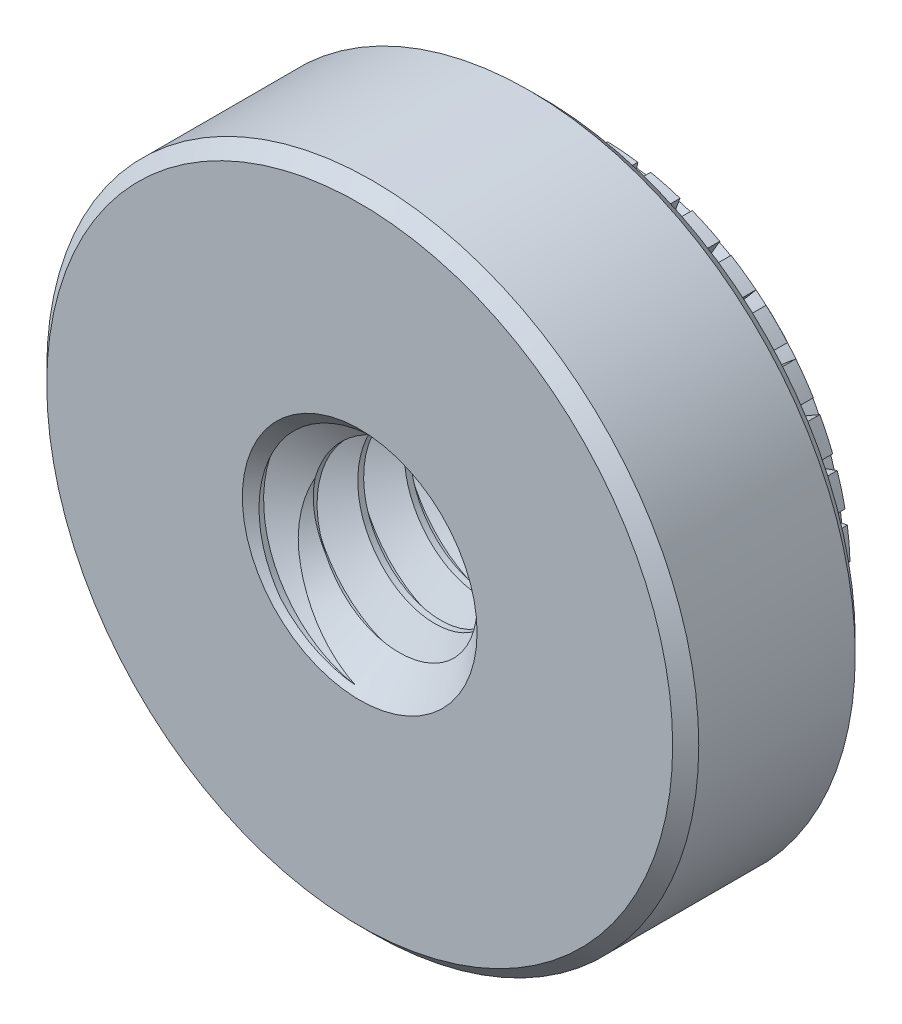
SolidWorks part; units mm, degrees
ref_plane "Front Plane" through (0, 0, 0) normal (0, 0, 1) x (1, 0, 0)
ref_plane "Top Plane" through (0, 0, 0) normal (0, 1, 0) x (1, 0, 0)
ref_plane "Right Plane" through (0, 0, 0) normal (1, 0, 0) x (0, 0, -1)
sketch "Sketch1" plane through (0, 0, 0) normal (0, 0, 1) x (1, 0, 0)
  circle A0 centre (0, 0) radius 3.175
  dimension "A" = 6.35
extrude "Extrude1" add sketch "Sketch1" against normal blind 1.778
sketch "Sketch15" plane through (0, 0, -1.778) normal (0, 0, -1) x (-1, 0, 0)
  circle A0 centre (0, 0) radius 2.1082
  dimension "hole dia" = 4.2164
sketch "Sketch2" plane through (0, 0, -1.778) normal (0, 0, -1) x (-1, 0, 0)
  circle A0 centre (0, 0) radius 2.4257
  dimension "D1" = 4.8514
extrude "Extrude2" add sketch "Sketch2" along normal blind 0.762
sketch "Sketch3" plane through (0, 0, -2.54) normal (0, 0, -1) x (-1, 0, 0)
  line L0 (0, 2.2352) -> (0, 3.175)
  circle A1 centre (0, 0) radius 3.175 construction
  circle A2 centre (0, 0) radius 2.2352
  circle A3 centre (0, 0) radius 2.2352 construction
  dimension "D1" = 0.1905
extrude "Cut-Extrude-Thin1" cut sketch "Sketch3" against normal up to surface (0.762 mm away) thin up to face at (3.175, 0, -1.778) thin type mid plane wall 0.127
pattern_circular "CirPattern1" count 36 over 360 about axis through (0, 0, -1.778) along (0, 0, 1) of "Cut-Extrude-Thin1"
sketch "Sketch5" plane through (0, 0, -2.54) normal (0, 0, -1) x (-1, 0, 0)
  circle A0 centre (0, 0) radius 3.175 construction
  circle A3 centre (0, 0) radius 2.159
  dimension "C" = 4.318
extrude "Cut-Extrude1" cut sketch "Sketch5" against normal blind 0.1905 draft 20 flip side to cut draft outward yes
chamfer "Chamfer2" distance 0.127 angle 45 2 edges at (3.175, 0, 0) (3.175, 0, -1.778)
sketch "Sketch7" plane through (0, 0, 0) normal (0, 0, 1) x (1, 0, 0)
  circle A0 centre (0, 0) radius 1.0922
  dimension "Thread Od" = 2.1844
extrude "Cut-Extrude3" cut sketch "Sketch7" against normal through all
sketch "Sketch8" plane through (0, 0, -2.54) normal (0, 0, -1) x (-1, 0, 0)
  circle A0 centre (0, 0) radius 1.0922 construction
  circle A1 centre (0, 0) radius 1.0922
curve "Helix/Spiral1" pitch 0.4536 height 5.715 radius 1.0922 centre (0, 0, -2.54) axis (0, 0, 1) start towards (0, 1, 0) parameters "pitch"=0.4536
sketch "Sketch9" plane through (0, 0, 0) normal (1, 0, 0) x (0, 0, -1)
  line L0 (2.9369, 1.0922) -> (2.7668, 0.7976)
  line L1 (2.7668, 0.7976) -> (2.7101, 0.7976)
  line L2 (2.7101, 0.7976) -> (2.54, 1.0922)
  line L3 (2.9369, 1.0922) -> (2.54, 1.0922)
  line L4 (2.7384, 1.0922) -> (2.7384, 0.7976) construction
  line L5 (2.8518, 0.9449) -> (2.625, 0.9449) construction
  line L6 (2.54, -1.0922) -> (2.54, 1.0922) construction
  dimension "D1" = 60
  dimension "D2" = 0.0567
  dimension "D3" = 0.2268
sweep "Sweep1" add profiles "Sketch9" path "Helix/Spiral1"
sketch "Sketch10" plane through (0, 0, 0) normal (0, 0, 1) x (1, 0, 0)
  circle A0 centre (0, 0) radius 3.175 construction
  circle A1 centre (0, 0) radius 3.175
extrude "Cut-Extrude4" cut sketch "Sketch10" along normal through all
sketch "Sketch11" plane through (0, 0, -2.54) normal (0, 0, -1) x (-1, 0, 0)
  circle A1 centre (0, 0) radius 2.159 construction
  circle A2 centre (0, 0) radius 2.159
extrude "Cut-Extrude5" cut sketch "Sketch11" along normal through all
sketch "Sketch13" plane through (0, 0, 0) normal (0, 0, 1) x (1, 0, 0)
  circle A2 centre (0, 0) radius 1.143
  circle A3 centre (0, 0) radius 1.143
  dimension "D1" = 0.0508
extrude "Cut-Extrude6" cut sketch "Sketch13" against normal through all draft 45
sketch "Sketch14" plane through (0, 0, -2.54) normal (0, 0, -1) x (-1, 0, 0)
  circle A2 centre (0, 0) radius 1.143
  circle A3 centre (0, 0) radius 1.143
  dimension "D1" = 0.0508
extrude "Cut-Extrude7" cut sketch "Sketch14" against normal through all draft 45
equation "\"D3@Helix/Spiral1\" = \"B@Extrude1\"+\"panel min.@Extrude2\"+.125"
equation "\"D2@Sketch9\" = \"pitch@Helix/Spiral1\"*.125"
equation "\"D3@Sketch9\" = \"pitch@Helix/Spiral1\"*.50"
equation "\"D1@Sketch2\" = \"hole dia@Sketch15\"+.025"
equation "\"D1@Cut-Extrude1\" = \"panel min.@Extrude2\"*.25"
